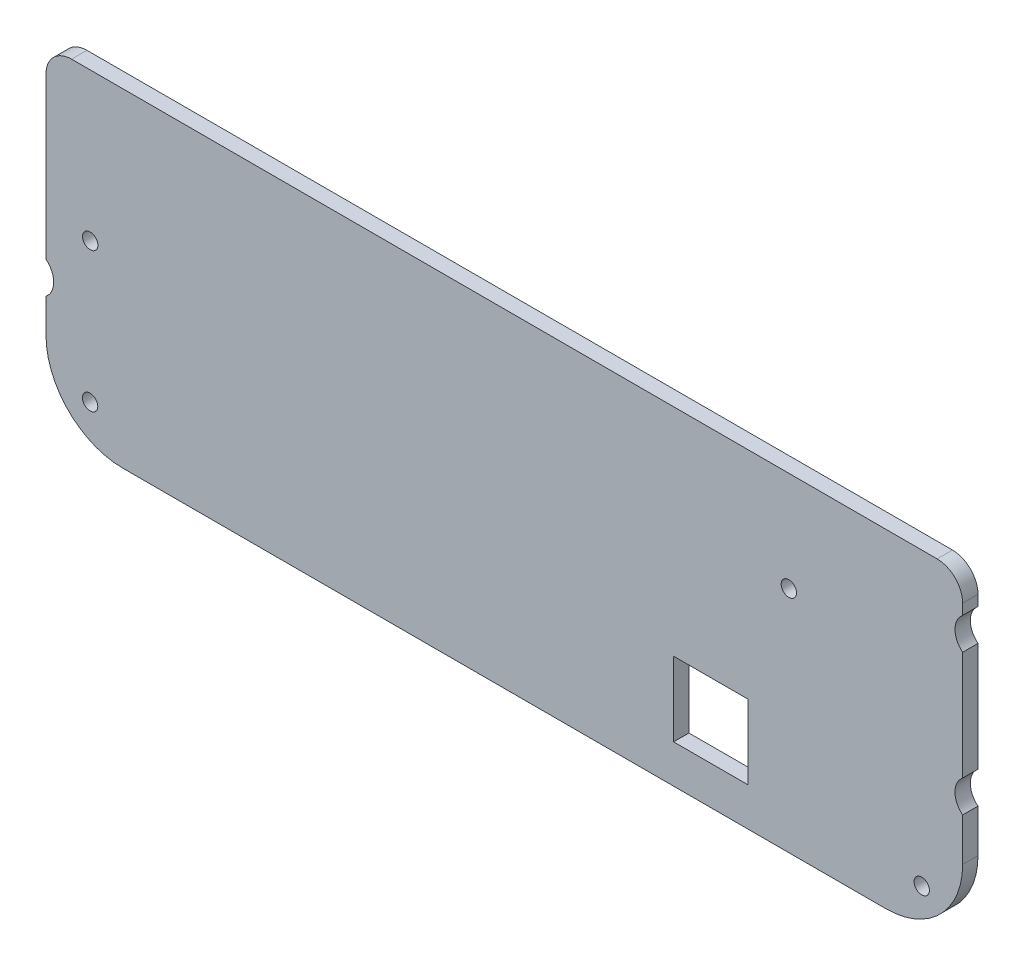
SolidWorks part; units mm, degrees
ref_plane "Plan de face" through (0, 0, 0) normal (0, 0, 1) x (1, 0, 0)
ref_plane "Plan de dessus" through (0, 0, 0) normal (0, 1, 0) x (1, 0, 0)
ref_plane "Plan de droite" through (0, 0, 0) normal (1, 0, 0) x (0, 0, -1)
sketch "Esquisse1" plane through (0, 0, 0) normal (0, 0, 1) x (1, 0, 0)
  line L1 (118.1017, 78.4023) -> (267.2717, 78.4023)
  line L2 (103.1017, 93.4023) -> (103.1017, 137.6323)
  line L3 (108.1017, 142.6323) -> (277.2717, 142.6323)
  line L4 (282.2717, 93.4023) -> (282.2717, 137.6323)
  arc A0 (277.2717, 142.6323) -> (282.2717, 137.6323) centre (277.2717, 137.6323) cw
  arc A1 (103.1017, 137.6323) -> (108.1017, 142.6323) centre (108.1017, 137.6323) cw
  arc A2 (267.2717, 78.4023) -> (282.2717, 93.4023) centre (267.2717, 93.4023) ccw
  arc A3 (118.1017, 78.4023) -> (103.1017, 93.4023) centre (118.1017, 93.4023) cw
  point P6 (282.2717, 142.6323)
  point P9 (103.1017, 142.6323)
  point P12 (282.2717, 78.4023)
  point P19 (192.6867, 110.5173)
  dimension "D3" = 5
  dimension "D4" = 15
  dimension "D1" = 179.17
  dimension "D2" = 64.23
extrude "Boss.-Extru.1" add sketch "Esquisse1" along normal blind 3
sketch "Esquisse2" plane through (0, 0, 0) normal (0, 0, -1) x (-1, 0, 0)
  line L0 (-103.1017, 137.6323) -> (-103.1017, 93.4023) construction
  line L1 (-118.1017, 78.4023) -> (-267.2717, 78.4023) construction
  line L2 (-282.2717, 93.4023) -> (-282.2717, 137.6323) construction
  line L3 (-277.2717, 142.6323) -> (-108.1017, 142.6323) construction
  circle A0 centre (-111.7417, 113.6923) radius 1.5
  circle A1 centre (-111.7217, 86.4023) radius 1.5
  circle A2 centre (-248.3017, 123.1223) radius 1.5
  circle A3 centre (-274.2717, 85.7523) radius 1.5
  dimension "D1" = 8.62
  dimension "D2" = 8
  dimension "D3" = 7.35
  dimension "D4" = 8
  dimension "D5" = 19.51
  dimension "D6" = 33.97
  dimension "D7" = 8.64
  dimension "D8" = 28.94
extrude "Enlèv. mat.-Extru.1" cut sketch "Esquisse2" against normal blind 10
sketch "Esquisse7" plane through (0, 0, 3) normal (0, 0, 1) x (1, 0, 0)
  line L0 (128.0704, 78.4023) -> (128.0704, 103.1223)
  line L1 (118.1017, 78.4023) -> (267.2717, 78.4023) construction
  line L2 (128.0704, 103.1223) -> (103.1017, 103.1223)
  line L3 (103.1017, 137.6323) -> (103.1017, 93.4023) construction
  line L4 (103.1017, 103.1223) -> (98.1017, 103.1223)
  line L5 (263.0387, 78.4023) -> (263.0387, 104.9023)
  line L6 (263.0387, 104.9023) -> (282.2717, 104.9023)
  line L7 (282.2717, 93.4023) -> (282.2717, 137.6323) construction
  line L8 (282.2717, 104.9023) -> (287.2717, 104.9023)
  line L9 (263.7381, 142.6323) -> (263.7381, 132.4423)
  line L10 (277.2717, 142.6323) -> (108.1017, 142.6323) construction
  line L11 (263.7381, 132.4423) -> (282.2717, 132.4423)
  line L12 (282.2717, 132.4423) -> (287.2717, 132.4423)
  circle A0 centre (100.6017, 103.1223) radius 4
  circle A1 centre (284.7717, 104.9023) radius 4
  circle A2 centre (284.7717, 132.4423) radius 4
extrude "Enlèv. mat.-Extru.2" cut sketch "Esquisse7" against normal blind 10
sketch "Esquisse8" plane through (0, 0, 0) normal (0, 0, -1) x (-1, 0, 0)
  line L0 (-282.2717, 93.4023) -> (-282.2717, 101.7798) construction
  line L1 (-240.2717, 85.9023) -> (-225.7717, 85.9023)
  line L2 (-240.2717, 85.9023) -> (-240.2717, 100.4023)
  line L3 (-240.2717, 100.4023) -> (-225.7717, 100.4023)
  line L4 (-225.7717, 85.9023) -> (-225.7717, 100.4023)
  line L5 (-118.1017, 78.4023) -> (-267.2717, 78.4023) construction
  dimension "D1" = 14.5
  dimension "D2" = 14.5
  dimension "D3" = 42
  dimension "D4" = 7.5
extrude "Enlèv. mat.-Extru.3" cut sketch "Esquisse8" against normal blind 10
